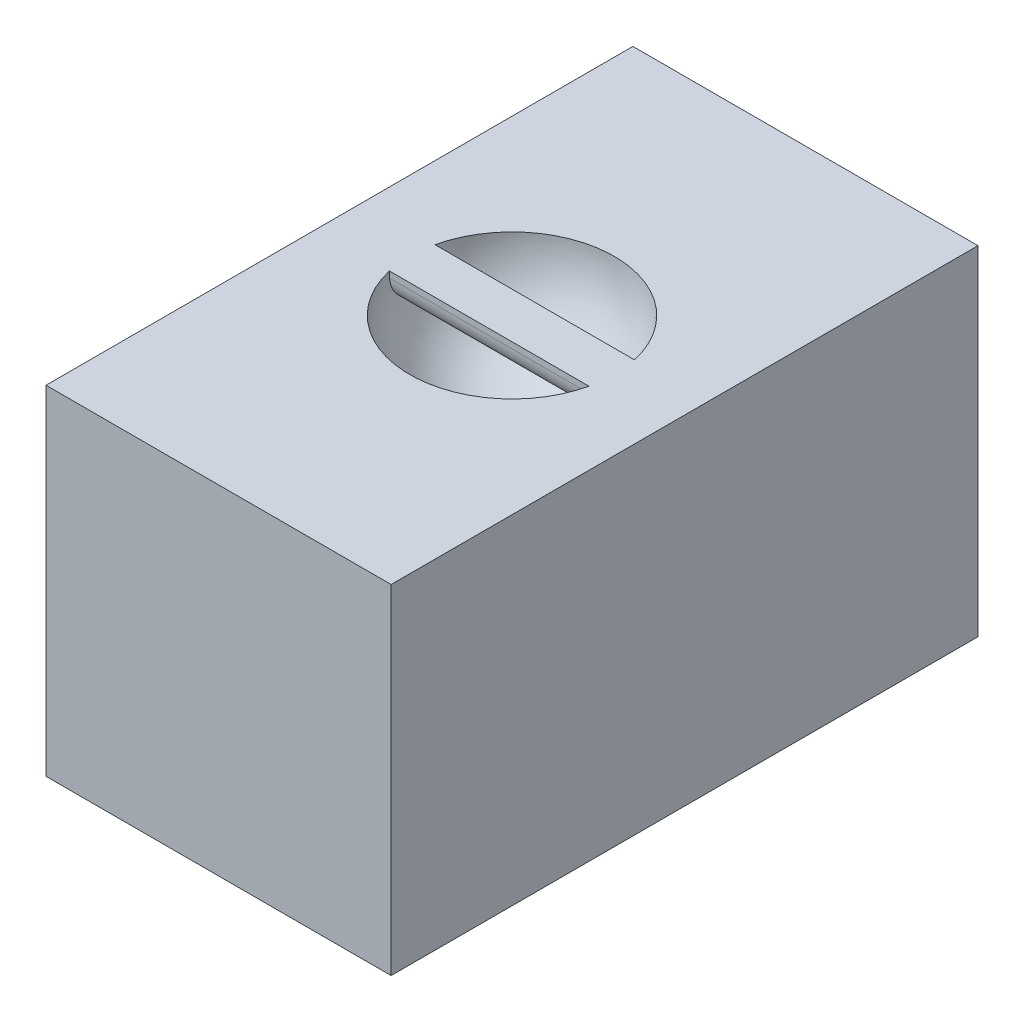
SolidWorks part; units mm, degrees
ref_plane "Front Plane" through (0, 0, 0) normal (0, 0, 1) x (1, 0, 0)
ref_plane "Top Plane" through (0, 0, 0) normal (0, 1, 0) x (1, 0, 0)
ref_plane "Right Plane" through (0, 0, 0) normal (1, 0, 0) x (0, 0, -1)
sketch "Sketch1" plane through (0, 0, 0) normal (0, 1, 0) x (1, 0, 0)
  line L1 (-28.599, -48.6314) -> (28.599, -48.6314)
  line L2 (-28.599, -48.6314) -> (-28.599, 48.6314)
  line L3 (-28.599, 48.6314) -> (28.599, 48.6314)
  line L4 (28.599, -48.6314) -> (28.599, 48.6314)
  point P1 (0, 0)
extrude "Boss-Extrude1" add sketch "Sketch1" along normal blind 56.134
sketch "Sketch6" plane through (0, 56.134, 0) normal (0, 1, 0) x (1, 0, 0)
  line L0 (-16.9638, 0) -> (16.9638, 0)
  arc A0 (-16.9638, 0) -> (16.9638, 0) centre (0, 0) ccw
revolve "Cut-Revolve13" cut sketch "Sketch6" angle 180 about L0
sketch "Sketch7" plane through (0, 56.134, 0) normal (0, 1, 0) x (1, 0, 0)
  line L0 (-18.72, 3.7774) -> (-18.72, -3.7774)
  line L1 (-18.72, 3.7774) -> (18.72, 3.7774)
  line L2 (-18.72, -3.7774) -> (18.72, -3.7774)
  line L3 (18.72, 3.7774) -> (18.72, -3.7774)
  line L4 (-18.72, 3.7774) -> (18.72, -3.7774) construction
  line L5 (18.72, 3.7774) -> (-18.72, -3.7774) construction
  circle A1 centre (0, 0) radius 16.9638 construction
  point P0 (0, 0)
  point P6 (0, 0)
  point P7 (0, 0)
  point P8 (0, 0)
  point P9 (20.9022, 3.7774)
  point P10 (0, 0)
  point P11 (0, 0)
  point P12 (0, 0)
  dimension "D1" = 7.5547
  dimension "D2" = 18.72
extrude "Boss-Extrude2" add sketch "Sketch7" against normal blind 5.08
fillet "Fillet1" radius 4.064 2 edges at (0, 51.054, -3.7774) (0, 51.054, 3.7774)
